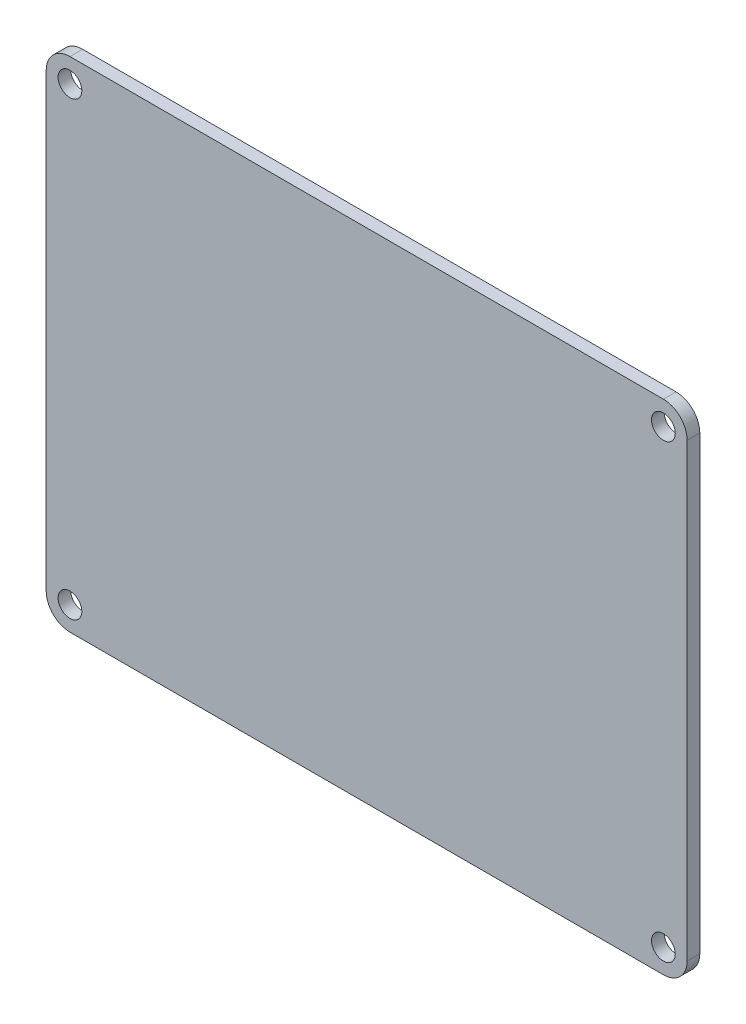
SolidWorks part; units mm, degrees
ref_plane "Vehicle Ground Plane" through (0, 0, 0) normal (0, 0, 1) x (1, 0, 0)
ref_plane "Vehicle Centreline Plane" through (0, 0, 0) normal (0, 1, 0) x (1, 0, 0)
ref_plane "Roll Hoop Plane" through (0, 0, 0) normal (1, 0, 0) x (0, 0, -1)
ref_axis "X-Axis" through (-88.99, 0, 0) along (1, 0, 0)
ref_axis "Y-Axis" through (0, 55, 0) along (0, -1, 0)
ref_axis "Z-Axis" through (0, 0, -88.99) along (0, 0, 1)
sketch "Sketch1" plane through (0, 0, 0) normal (0, 0, 1) x (1, 0, 0)
  line L1 (-37.5, -31.5) -> (37.5, -31.5)
  line L2 (-40.5, -28.5) -> (-40.5, 28.5)
  line L3 (-37.5, 31.5) -> (37.5, 31.5)
  line L4 (40.5, -28.5) -> (40.5, 28.5)
  line L5 (-40.5, -31.5) -> (40.5, 31.5) construction
  line L6 (-40.5, 31.5) -> (40.5, -31.5) construction
  circle A0 centre (-37.5, 28.5) radius 1.5
  circle A1 centre (37.5, 28.5) radius 1.5
  circle A2 centre (37.5, -28.5) radius 1.5
  circle A3 centre (-37.5, -28.5) radius 1.5
  arc A4 (-37.5, -31.5) -> (-40.5, -28.5) centre (-37.5, -28.5) cw
  arc A5 (37.5, -31.5) -> (40.5, -28.5) centre (37.5, -28.5) ccw
  arc A6 (37.5, 31.5) -> (40.5, 28.5) centre (37.5, 28.5) cw
  arc A7 (-40.5, 28.5) -> (-37.5, 31.5) centre (-37.5, 28.5) cw
  point P8 (0, 0)
  dimension "D1" = 3
  dimension "D8" = 3
  dimension "D2" = 57
  dimension "D3" = 75
  dimension "D4" = 37.5
  dimension "D5" = 28.5
  dimension "D6" = 3
  dimension "D7" = 3
extrude "Boss-Extrude1" add sketch "Sketch1" along normal blind 1.6
equation "\"D4@Sketch1\"=\"D3@Sketch1\"/2"
equation "\"D5@Sketch1\"=\"D2@Sketch1\"/2"
